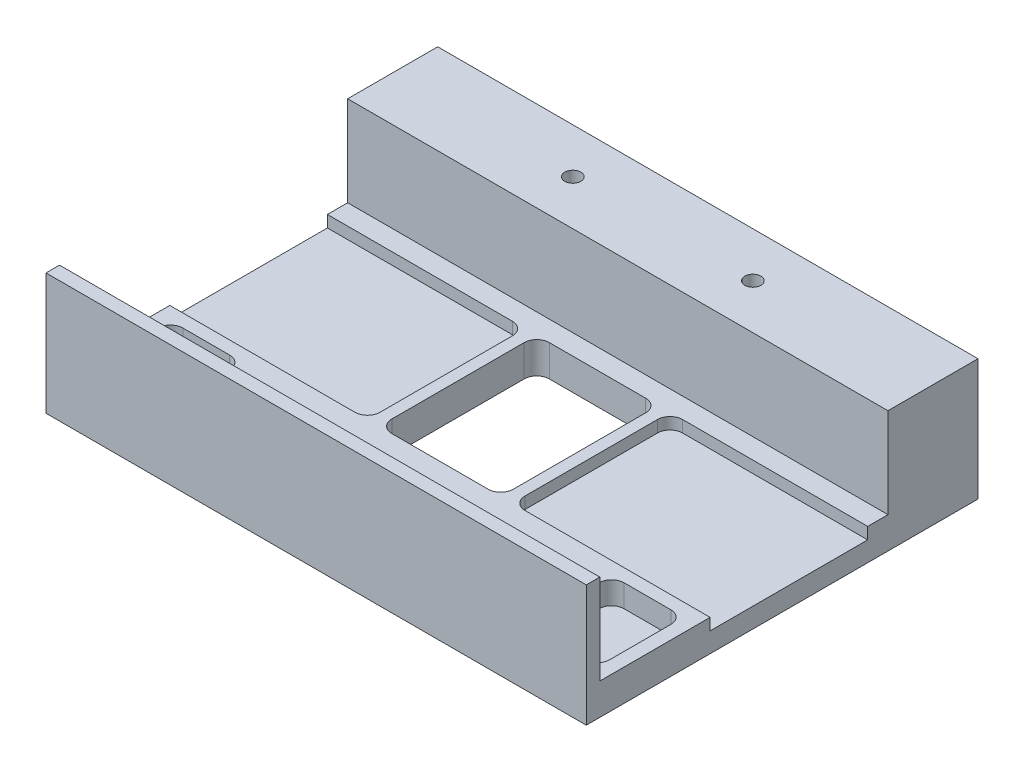
SolidWorks part; units mm, degrees
material "1345 Alloy"
ref_plane "Front Plane" through (0, 0, 0) normal (0, 0, 1) x (1, 0, 0)
ref_plane "Top Plane" through (0, 0, 0) normal (0, 1, 0) x (1, 0, 0)
ref_plane "Right Plane" through (0, 0, 0) normal (1, 0, 0) x (0, 0, -1)
sketch "Sketch1" plane through (0, 0, 0) normal (0, 1, 0) x (1, 0, 0)
  line L1 (-38.1, 22.225) -> (38.1, 22.225)
  line L2 (-38.1, 22.225) -> (-38.1, -22.225)
  line L3 (-38.1, -22.225) -> (38.1, -22.225)
  line L4 (38.1, 22.225) -> (38.1, -22.225)
  line L5 (-38.1, 22.225) -> (38.1, -22.225) construction
  line L6 (-38.1, -22.225) -> (38.1, 22.225) construction
  point P0 (0, 0)
  dimension "D1" = 44.45
  dimension "D2" = 76.2
extrude "Boss-Extrude1" add sketch "Sketch1" along normal blind 4.445
sketch "Sketch2" plane through (0, 4.445, 0) normal (0, 1, 0) x (1, 0, 0)
  line L0 (38.1, -22.225) -> (38.1, 22.225) construction
  line L1 (-38.1, 22.225) -> (38.1, 22.225)
  line L2 (-38.1, 22.225) -> (-38.1, 20.32)
  line L3 (-38.1, 20.32) -> (38.1, 20.32)
  line L4 (38.1, 22.225) -> (38.1, 20.32)
  line L5 (-38.1, 0) -> (38.1, 0) construction
  line L6 (-38.1, 22.225) -> (-38.1, -22.225) construction
  line L7 (38.1, -22.225) -> (38.1, -20.32)
  line L8 (-38.1, -20.32) -> (38.1, -20.32)
  line L9 (-38.1, -22.225) -> (-38.1, -20.32)
  line L10 (-38.1, -22.225) -> (38.1, -22.225)
  dimension "D1" = 1.905
extrude "Boss-Extrude2" add sketch "Sketch2" along normal blind 12.7
sketch "Sketch6" plane through (0, 4.445, 0) normal (0, 1, 0) x (1, 0, 0)
  line L0 (-38.1, 20.32) -> (-38.1, -20.32) construction
  line L1 (38.1, -20.32) -> (38.1, 20.32) construction
  line L2 (-38.1, 20.32) -> (38.1, 20.32) construction
  line L3 (-7.5, 16.35) -> (7.5, 16.35) construction
  line L4 (-7.5, 16.35) -> (-7.5, -3.65) construction
  line L5 (-7.5, -3.65) -> (7.5, -3.65) construction
  line L6 (7.5, 16.35) -> (7.5, -3.65) construction
  line L7 (-38.1, 6.35) -> (38.1, 6.35) construction
  line L8 (-7.5, 16.35) -> (7.5, -3.65) construction
  line L9 (-7.5, -3.65) -> (7.5, 16.35) construction
  line L10 (-38.1, -7.62) -> (38.1, -7.62) construction
  line L11 (-6.7945, -2.9845) -> (6.7945, 15.6845) construction
  line L12 (-8.5725, 15.6845) -> (-8.5725, -2.9845)
  line L13 (-6.7945, -4.7625) -> (6.7945, -4.7625)
  line L14 (8.5725, 15.6845) -> (8.5725, -2.9845)
  line L15 (-6.7945, 17.4625) -> (6.7945, 17.4625)
  line L16 (38.1, 20.32) -> (38.1, -7.62) construction
  line L17 (-38.1, 20.32) -> (-38.1, -7.62) construction
  line L18 (-6.7945, 15.6845) -> (6.7945, -2.9845) construction
  arc A0 (-6.7945, -4.7625) -> (-8.5725, -2.9845) centre (-6.7945, -2.9845) cw
  arc A1 (6.7945, -4.7625) -> (8.5725, -2.9845) centre (6.7945, -2.9845) ccw
  arc A2 (8.5725, 15.6845) -> (6.7945, 17.4625) centre (6.7945, 15.6845) ccw
  arc A3 (-6.7945, 17.4625) -> (-8.5725, 15.6845) centre (-6.7945, 15.6845) ccw
  point P0 (0, 6.35)
  point P16 (0, 6.35)
  dimension "D5" = 17.145
  dimension "D4" = 1.778
  dimension "D1" = 15
  dimension "D2" = 20
  dimension "D3" = 27.94
  dimension "D6" = 22.225
extrude "Cut-Extrude3" cut sketch "Sketch6" against normal through all
sketch "Sketch7" plane through (0, 4.445, 0) normal (0, 1, 0) x (1, 0, 0)
  line L0 (0, 6.35) -> (-38.1, 6.35) construction
  line L1 (-38.1, 20.32) -> (-38.1, -20.32) construction
  line L2 (-38.1, 17.4625) -> (-10.2235, 17.4625)
  line L3 (-38.1, 17.4625) -> (-38.1, -4.7625)
  line L4 (-38.1, -4.7625) -> (-10.2235, -4.7625)
  line L7 (0, 17.4625) -> (0, -4.7625) construction
  line L8 (-10.2235, 17.4625) -> (-10.2235, -4.7625)
  line L10 (6.7945, 17.4625) -> (-6.7945, 17.4625) construction
  line L11 (-6.7945, -4.7625) -> (6.7945, -4.7625) construction
  line L12 (-8.5725, 15.6845) -> (-8.5725, -2.9845) construction
  line L13 (10.2235, 17.4625) -> (10.2235, -4.7625)
  line L14 (38.1, 17.4625) -> (10.2235, 17.4625)
  line L16 (38.1, -4.7625) -> (10.2235, -4.7625)
  line L17 (38.1, 17.4625) -> (38.1, -4.7625)
  dimension "D2" = 1.651
extrude "Cut-Extrude4" cut sketch "Sketch7" against normal blind 1.651
sketch "Sketch11" plane through (0, 4.445, 0) normal (0, 1, 0) x (1, 0, 0)
  line L0 (0, 0) -> (0, -20.32) construction
  line L1 (-36.195, -6.604) -> (-36.195, -18.796)
  line L2 (-38.1, -4.7625) -> (-38.1, -20.32) construction
  line L3 (38.1, -20.32) -> (-38.1, -20.32) construction
  line L6 (-36.195, -18.796) -> (-26.035, -18.796)
  line L7 (-26.035, -18.796) -> (-26.035, -6.604)
  line L8 (-26.035, -6.604) -> (-36.195, -6.604)
  line L9 (-38.1, -22.225) -> (38.1, -22.225) construction
  line L10 (26.035, -6.604) -> (36.195, -6.604)
  line L11 (26.035, -18.796) -> (26.035, -6.604)
  line L12 (36.195, -18.796) -> (26.035, -18.796)
  line L13 (36.195, -6.604) -> (36.195, -18.796)
  dimension "D1" = 1.905
  dimension "D2" = 12.192
  dimension "D3" = 10.16
  dimension "D4" = 3.429
extrude "Cut-Extrude6" cut sketch "Sketch11" against normal blind 3.175
sketch "Sketch13" plane through (0, 0, -20.32) normal (0, 0, 1) x (1, 0, 0)
  line L4 (-38.1, 0) -> (38.1, 0)
  line L5 (-38.1, 17.145) -> (-38.1, 0)
  line L6 (38.1, 17.145) -> (-38.1, 17.145)
  line L7 (38.1, 0) -> (38.1, 17.145)
  line L8 (-38.1, 0) -> (38.1, 0)
  line L9 (-38.1, 17.145) -> (-38.1, 0)
  line L10 (38.1, 17.145) -> (-38.1, 17.145)
  line L11 (38.1, 0) -> (38.1, 17.145)
  dimension "D1" = 0
extrude "Boss-Extrude3" add sketch "Sketch13" against normal blind 12.7
sketch3d "3DSketch1"
  line L0 (-31.115, 4.445, 18.796) -> (-31.115, 4.445, 20.32) construction
  line L1 (-36.195, 4.445, 18.796) -> (-26.035, 4.445, 18.796) construction
  line L2 (38.1, 4.445, 20.32) -> (-38.1, 4.445, 20.32) construction
  line L3 (-31.115, 4.445, 20.32) -> (-31.115, 17.145, 20.32) construction
  line L4 (38.1, 17.145, 20.32) -> (-38.1, 17.145, 20.32) construction
fillet "Fillet1" radius 1.778 12 edges at (-36.195, 2.8575, 6.604) (-26.035, 2.8575, 6.604) (26.035, 2.8575, 18.796) (36.195, 2.8575, 18.796) (26.035, 2.8575, 6.604) (36.195, 2.8575, 6.604) (-36.195, 2.8575, 18.796) (-26.035, 2.8575, 18.796) (-10.2235, 3.6195, 4.7625) (-10.2235, 3.6195, -17.4625) (10.2235, 3.6195, -17.4625) (10.2235, 3.6195, 4.7625)
hole_wizard "1/4-20 Tapped Hole1" positions "Sketch16" profile "Sketch15" tap size "1/4-20" standard "Ansi Inch"
sketch "Sketch16" plane through (0, 0, -33.02) normal (0, 0, -1) x (-1, 0, 0)
  line L0 (0, 0) -> (0, 17.145) construction
  line L1 (38.1, 0) -> (-38.1, 0) construction
  line L2 (-38.1, 17.145) -> (38.1, 17.145) construction
  line L5 (-38.1, 0) -> (-38.1, 17.145) construction
  point P0 (-25.4, 8.89)
  point P16 (25.4, 8.89)
  dimension "D1" = 12.7
  dimension "D2" = 8.89
sketch "Sketch15" plane through (25.4, 8.89, -33.02) normal (1, 0, 0) x (0, 1, 0)
  line L0 (0, 0) -> (0, 7.8838)
  line L1 (0, 7.8838) -> (2.5527, 6.35)
  line L2 (2.5527, 6.35) -> (2.5527, 0)
  line L5 (2.5527, 0) -> (0, 0)
  line L10 (0, 7.8838) -> (-2.5527, 6.35) construction
  line L11 (0, -6.35) -> (0, 107.95) construction
  dimension "Tap Drill Dia." = 5.1054
  dimension "Tap Drill Depth" = 6.35
  dimension "Drill Angle" = 118
cosmetic thread "Hole Thread1" parameters "D1"=6.35, "D2"=6.35
cosmetic thread "Hole Thread2" parameters "D1"=6.35, "D2"=6.35
hole_wizard "#4-40 Tapped Hole1" positions "Sketch18" profile "Sketch17" tap size "#4-40" standard "Ansi Inch"
sketch "Sketch18" plane through (0, 17.145, 0) normal (0, 1, 0) x (-1, 0, 0)
  point P6 (12.7, -26.67)
  point P10 (-12.7, -26.67)
sketch "Sketch17" plane through (-12.7, 17.145, -26.67) normal (1, 0, 0) x (0, 0, 1)
  line L0 (0, 0) -> (0, 7.0292)
  line L1 (0, 7.0292) -> (1.1303, 6.35)
  line L2 (1.1303, 6.35) -> (1.1303, 0)
  line L5 (1.1303, 0) -> (0, 0)
  line L10 (0, 7.0292) -> (-1.1303, 6.35) construction
  line L11 (0, -6.35) -> (0, 107.95) construction
  dimension "Tap Drill Dia." = 2.2606
  dimension "Tap Drill Depth" = 6.35
  dimension "Drill Angle" = 118
cosmetic thread "Hole Thread3" parameters "D1"=6.35, "D2"=2.8448
cosmetic thread "Hole Thread4" parameters "D1"=6.35, "D2"=2.8448
sketch "refSketch" plane through (0, 4.445, 0) normal (0, 1, 0) x (1, 0, 0)
  line L0 (-6.7945, 15.6845) -> (6.7945, -2.9845) construction
  line L1 (-6.7945, -2.9845) -> (6.7945, 15.6845) construction
  point P8 (0, 6.35)
ref_axis "Axis1" through (0, -44.4835, -6.35) along (0, 1, 0)
